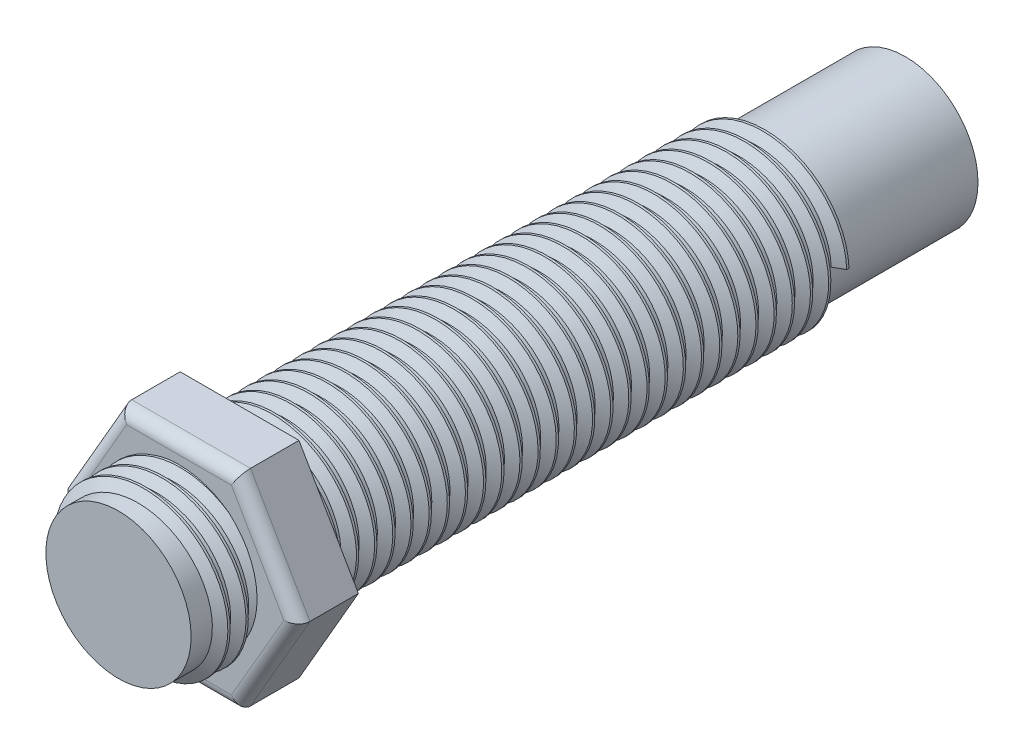
SolidWorks part; units mm, degrees
ref_plane "前视基准面" through (0, 0, 0) normal (0, 0, 1) x (1, 0, 0)
ref_plane "上视基准面" through (0, 0, 0) normal (0, 1, 0) x (1, 0, 0)
ref_plane "右视基准面" through (0, 0, 0) normal (1, 0, 0) x (0, 0, -1)
sketch "草图1" plane through (0, 0, 0) normal (0, 0, 1) x (1, 0, 0)
  line L1 (4.9075, -8.5) -> (9.815, 0)
  line L2 (9.815, 0) -> (4.9075, 8.5)
  line L3 (4.9075, 8.5) -> (-4.9075, 8.5)
  line L4 (-4.9075, 8.5) -> (-9.815, 0)
  line L5 (-9.815, 0) -> (-4.9075, -8.5)
  line L6 (-4.9075, -8.5) -> (4.9075, -8.5)
  circle A0 centre (0, 0) radius 8.5 construction
  circle A1 centre (0, 0) radius 6
  dimension "D1" = 17
  dimension "D2" = 12
extrude "凸台-拉伸2" add sketch "草图1" against normal blind 5 contours L1 L2 L3 L4 L5 L6
extrude "凸台-拉伸3" add sketch "草图1<4>" along normal blind 5 and the other way blind 50 contours A1 region at (0, 0, 0)
sketch "草图1<4>" plane through (0, 0, 0) normal (0, 0, 1) x (1, 0, 0) same geometry as "草图1"
fillet "圆角1" radius 1 6 edges at (7.3612, 4.25, 0) (7.3612, -4.25, 0) (0, -8.5, 0) (-7.3612, -4.25, 0) (-7.3612, 4.25, 0) (0, 8.5, 0)
thread "螺纹线1" pitch 1.5 method extrude profile "螺纹线轮廓4" start angle 0, offset 1, length 0, pitch 1.5, diameter 12
ref_plane "基准面4" through (6, 0, -49) normal (0, -1, 0) x (1, 0, 0)
sketch "螺纹线轮廓4" plane through (6, 0, -49) normal (0, -1, 0) x (1, 0, 0)
  line L0 (0, 0) -> (0, 1.5) construction
  line L1 (0, 0) -> (0.8119, 0.4687)
  line L2 (0.8119, 0.4687) -> (0.8119, 0.6562)
  line L3 (0.8119, 0.6562) -> (0, 1.125)
  line L4 (0.8119, 0.5625) -> (0, 0.5625) construction
  line L11 (0, 0) -> (0, 1.125)
  point P2 (0, 0)
  dimension "Pitch" = 1.5
  dimension "Profile_Angle" = 60
  dimension "Profile_Land" = 0.1875
  dimension "Profile_Height" = 0.8119
thread "螺纹线2" pitch 1.5 method extrude profile "螺纹线轮廓5" start angle 0, offset 1, length 0, pitch 1.5, diameter 12
ref_plane "基准面5" through (-6, 0, 4) normal (0, -1, 0) x (-1, 0, 0)
sketch "螺纹线轮廓5" plane through (-6, 0, 4) normal (0, -1, 0) x (-1, 0, 0)
  line L0 (0, 0) -> (0, 1.5) construction
  line L1 (0, 0) -> (0.8119, 0.4687)
  line L2 (0.8119, 0.4687) -> (0.8119, 0.6562)
  line L3 (0.8119, 0.6562) -> (0, 1.125)
  line L4 (0.8119, 0.5625) -> (0, 0.5625) construction
  line L11 (0, 0) -> (0, 1.125)
  point P2 (0, 0)
  dimension "Pitch" = 1.5
  dimension "Profile_Angle" = 60
  dimension "Profile_Land" = 0.1875
  dimension "Profile_Height" = 0.8119
sketch "草图16" plane through (0, 0, -50) normal (0, 0, -1) x (-1, 0, 0)
  circle A0 centre (0, 0) radius 6
extrude "凸台-拉伸4" add sketch "草图16" along normal blind 10
